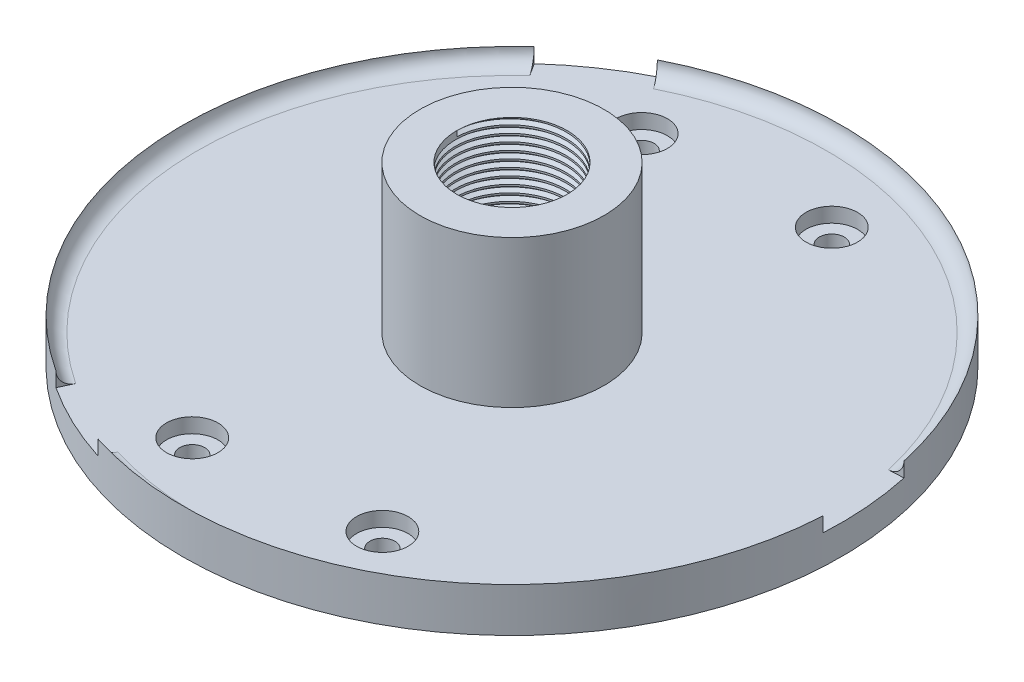
SolidWorks part; units mm, degrees
ref_plane "Front Plane" through (0, 0, 0) normal (0, 0, 1) x (1, 0, 0)
ref_plane "Top Plane" through (0, 0, 0) normal (0, 1, 0) x (1, 0, 0)
ref_plane "Right Plane" through (0, 0, 0) normal (1, 0, 0) x (0, 0, -1)
sketch "Sketch1" plane through (0, 0, 0) normal (0, 1, 0) x (1, 0, 0)
  circle A0 centre (0, 0) radius 44.75
  dimension "D1" = 89.5
extrude "Boss-Extrude1" add sketch "Sketch1" along normal blind 4
sketch "Sketch2" plane through (0, 4, 0) normal (0, 1, 0) x (1, 0, 0)
  circle A0 centre (0, 0) radius 12.5
  dimension "D1" = 25
extrude "Boss-Extrude2" add sketch "Sketch2" along normal blind 20
sketch "Sketch3" plane through (0, 24, 0) normal (0, 1, 0) x (1, 0, 0)
  circle A0 centre (0, 0) radius 7.5
  dimension "D1" = 15
extrude "Cut-Extrude1" cut sketch "Sketch3" against normal up to surface (24 mm away) up to face at (0, 0, 44.75)
sketch "Sketch4" plane through (0, 0, 0) normal (1, 0, 0) x (0, 0, -1)
  line L0 (44.75, 4) -> (44.75, 6)
  line L1 (44.75, 4) -> (42.75, 4)
  line L2 (44.75, 4) -> (-44.75, 4) construction
  arc A0 (42.75, 4) -> (44.75, 6) centre (42.75, 6) ccw
  dimension "D1" = 2
ref_axis "Axis1" through (0, 0, 0) along (0, 1, 0)
revolve "Revolve1" add sketch "Sketch4" angle 360 about axis through (0, 0, 0) along (0, 1, 0) region at (0, 4.4467, -44.3033)
thread "Thread1" pitch 1 method cut profile "Thread Profile1" start angle 0, offset 0, length 15, pitch 1, diameter 15
ref_plane "Plane1" through (-7.5, 24, 0) normal (0, 0, 1) x (-1, 0, 0)
sketch "Thread Profile1" plane through (-7.5, 24, 0) normal (0, 0, 1) x (-1, 0, 0)
  line L0 (0, 0) -> (0, 1) construction
  line L1 (0, 0) -> (0.5413, 0.3125)
  line L2 (0.5413, 0.3125) -> (0.5413, 0.4375)
  line L3 (0.5413, 0.4375) -> (0, 0.75)
  line L4 (0.5413, 0.375) -> (0, 0.375) construction
  line L11 (0, 0) -> (0, 0.75)
  point P2 (0, 0)
  dimension "Pitch" = 1
  dimension "Profile_Angle" = 60
  dimension "Profile_Land" = 0.125
  dimension "Profile_Height" = 0.5413
sketch "Sketch12" plane through (0, 0, 0) normal (0, -1, 0) x (1, 0, 0)
  line L1 (30, 15) -> (-30, 15)
  line L2 (30, 15) -> (30, -15)
  line L3 (30, -15) -> (-30, -15)
  line L4 (-30, 15) -> (-30, -15)
  line L5 (30, 15) -> (-30, -15) construction
  line L6 (30, -15) -> (-30, 15) construction
  point P0 (0, 0)
  dimension "D1" = 60
  dimension "D2" = 30
sketch "Sketch13" plane through (0, 4, 0) normal (0, -1, 0) x (1, 0, 0)
  line L0 (0, 0) -> (3.5593, 44.859) construction
  line L1 (0, 0) -> (15.9499, -1.2655) construction
  line L2 (14.6843, -17.2154) -> (17.2154, 14.6843) construction
  line L3 (12.9116, 11.0132) -> (11.9624, -0.9492) construction
  line L4 (12.9116, 11.0132) -> (14.5924, 32.1967) construction
  circle A0 centre (13.9991, 24.7202) radius 1.7
  circle A1 centre (14.5924, 32.1967) radius 1.7
  arc A2 (11.4465, 43.5199) -> (-4.4403, 44.7804) centre (0, 0) ccw construction
  circle A3 centre (12.9116, 11.0132) radius 1.7
  circle A17 centre (11.0132, -12.9116) radius 1.7
  circle A18 centre (9.3325, -34.095) radius 1.7
  circle A19 centre (9.9257, -26.6185) radius 1.7
  circle A20 centre (-13.9991, -24.7202) radius 1.7
  circle A21 centre (-14.5924, -32.1967) radius 1.7
  circle A22 centre (-12.9116, -11.0132) radius 1.7
  circle A23 centre (-11.0132, 12.9116) radius 1.7
  circle A24 centre (-9.3325, 34.095) radius 1.7
  circle A25 centre (-9.9257, 26.6185) radius 1.7
  dimension "D1" = 3.4
  dimension "D2" = 7.5
  dimension "D3" = 13.75
  dimension "D4" = 12
extrude "Cut-Extrude2" cut sketch "Sketch13" along normal up to surface (4 mm away) contours A1 | A21 | A18 | A24 up to face at (0, 0, 7.5)
sketch "Sketch14" plane through (0, 4, 0) normal (0, 1, 0) x (1, 0, 0)
  circle A0 centre (-9.3325, -34.095) radius 3.5
  circle A1 centre (-14.5924, 32.1967) radius 3.5
  circle A2 centre (9.3325, 34.095) radius 3.5
  circle A3 centre (14.5924, -32.1967) radius 3.5
  dimension "D1" = 7
extrude "Cut-Extrude3" cut sketch "Sketch14" against normal blind 2
sketch "Sketch16" plane through (0, 4, 0) normal (0, 1, 0) x (1, 0, 0)
  line L0 (-19.347, -40.6287) -> (0, 0) construction
  line L1 (-25.512, 37.0694) -> (0, 0) construction
  line L2 (44.859, 3.5593) -> (0, 0) construction
  line L3 (-30.4546, 33.6678) -> (-20.5694, 40.471)
  line L4 (-30.4546, 33.6678) -> (-24.1286, 23.8296)
  line L5 (-20.5694, 40.471) -> (-13.9383, 30.8359)
  line L6 (-24.1286, 23.8296) -> (-13.9383, 30.8359)
  line L7 (32.7014, 8.9812) -> (33.6738, -3.347)
  line L8 (45.3336, -2.4219) -> (33.6738, -3.347)
  line L9 (44.3844, 9.5405) -> (45.3336, -2.4219)
  line L10 (44.3844, 9.5405) -> (32.7014, 8.9812)
  line L11 (-8.5728, -32.8108) -> (-19.7355, -27.4889)
  line L12 (-24.7642, -38.0491) -> (-19.7355, -27.4889)
  line L13 (-13.9299, -43.2083) -> (-24.7642, -38.0491)
  line L14 (-13.9299, -43.2083) -> (-8.5728, -32.8108)
  point P10 (-25.512, 37.0694)
  point P24 (0, 0)
  dimension "D1" = 120
  dimension "D2" = 12
  dimension "D3" = 3
extrude "Cut-Extrude4" cut sketch "Sketch16" along normal blind 2
